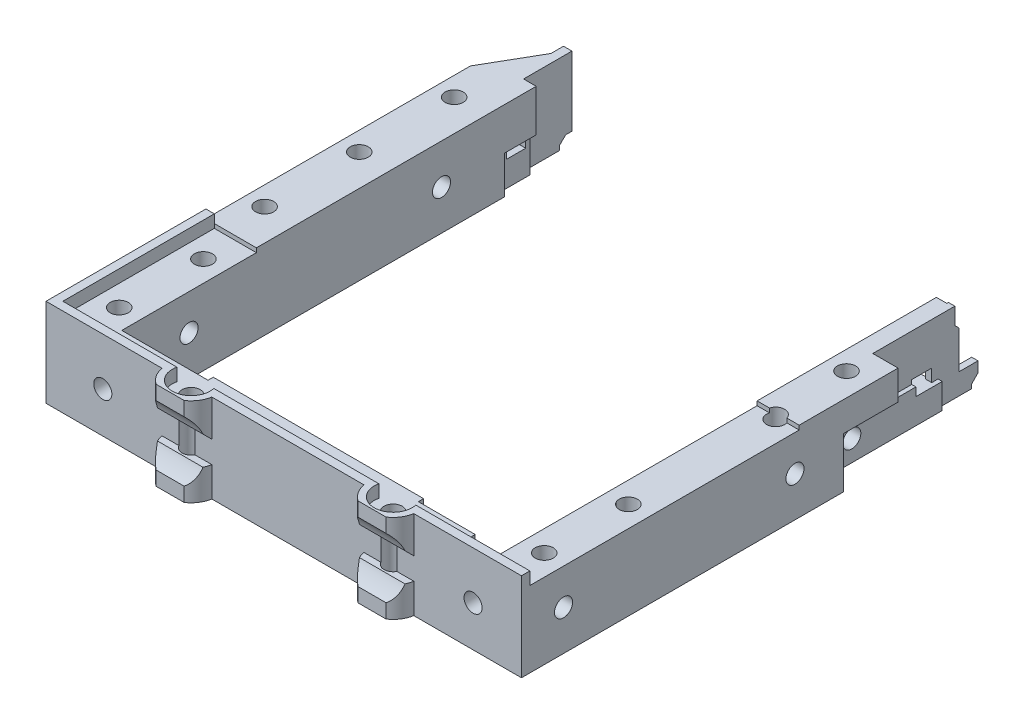
SolidWorks part; units mm, degrees
ref_plane "前视基准面" through (0, 0, 0) normal (0, 0, 1) x (1, 0, 0)
ref_plane "上视基准面" through (0, 0, 0) normal (0, 1, 0) x (1, 0, 0)
ref_plane "右视基准面" through (0, 0, 0) normal (1, 0, 0) x (0, 0, -1)
sketch "草图2" plane through (0, 0, 0) normal (0, 1, 0) x (1, 0, 0)
  line L0 (0, 0) -> (0, -10) construction
  line L1 (-45.5, 0) -> (45.5, 0)
  line L2 (45.5, 0) -> (45.5, 93)
  line L3 (45.5, 93) -> (55.5, 93)
  line L4 (55.5, 93) -> (55.5, -10)
  line L5 (55.5, -10) -> (-55.5, -10)
  line L6 (-45.5, 93) -> (-55.5, 93)
  line L7 (-55.5, 93) -> (-55.5, -10)
  line L8 (-45.5, 0) -> (-45.5, 93)
  dimension "D1" = 10
  dimension "D2" = 10
  dimension "D3" = 45.5
  dimension "D4" = 93
extrude "凸台-拉伸1" add sketch "草图2" along normal blind 18
sketch "草图3" plane through (0, 18, 0) normal (0, 1, 0) x (1, 0, 0)
  line L0 (55.5, 93) -> (45.5, 93) construction
  line L1 (45.5, 93) -> (45.5, 0) construction
  circle A0 centre (50, 76.75) radius 2.15
  dimension "D1" = 16.25
  dimension "D2" = 4.3
  dimension "D3" = 4.5
extrude "切除-拉伸1" cut sketch "草图3" against normal through all
sketch "草图4" plane through (55.5, 0, 0) normal (1, 0, 0) x (0, 0, -1)
  line L0 (-10, 0) -> (93, 0) construction
  line L1 (93, 18) -> (85.5, 18)
  line L2 (93, 18) -> (93, 0)
  line L3 (93, 0) -> (85.5, 0)
  line L4 (85.5, 18) -> (85.5, 0)
  line L5 (93, 18) -> (85.5, 0) construction
  line L6 (93, 0) -> (85.5, 18) construction
  point P4 (89.25, 9)
  dimension "D1" = 7.5
extrude "切除-拉伸2" cut sketch "草图4" against normal blind 6
sketch "草图5" plane through (55.5, 0, 0) normal (1, 0, 0) x (0, 0, -1)
  line L0 (85.5, 18) -> (85.5, 0) construction
  line L1 (85.5, 12) -> (70.5, 12)
  line L2 (85.5, 12) -> (85.5, 0)
  line L3 (85.5, 0) -> (70.5, 0)
  line L4 (70.5, 12) -> (70.5, 0)
  line L5 (85.5, 12) -> (70.5, 0) construction
  line L6 (85.5, 0) -> (70.5, 12) construction
  line L7 (-10, 0) -> (85.5, 0) construction
  line L8 (-10, 18) -> (85.5, 18) construction
  point P4 (78, 6)
  dimension "D1" = 6
  dimension "D2" = 15
extrude "切除-拉伸3" cut sketch "草图5" against normal up to surface (6 mm away) up to face at (49.5, 9, -89.25)
sketch "草图6" plane through (49.5, 0, 0) normal (1, 0, 0) x (0, 0, -1)
  line L1 (93, 0) -> (91, 0)
  line L2 (93, 0) -> (93, 9)
  line L3 (93, 9) -> (91, 9)
  line L4 (91, 0) -> (91, 9)
  line L5 (93, 0) -> (91, 9) construction
  line L6 (93, 9) -> (91, 0) construction
  point P4 (92, 4.5)
  dimension "D1" = 9
  dimension "D2" = 2
extrude "切除-拉伸4" cut sketch "草图6" against normal up to next
sketch "草图7" plane through (0, 18, 0) normal (0, 1, 0) x (1, 0, 0)
  line L0 (-45.5, 0) -> (-45.5, 93) construction
  line L1 (-55.5, 93) -> (-45.5, 93)
  line L2 (-55.5, 93) -> (-55.5, 32)
  line L3 (-55.5, 32) -> (-45.5, 32)
  line L4 (-45.5, 93) -> (-45.5, 32)
  line L5 (-55.5, 93) -> (-45.5, 32) construction
  line L6 (-55.5, 32) -> (-45.5, 93) construction
  point P4 (-50.5, 62.5)
  dimension "D1" = 61
extrude "凸台-拉伸2" add sketch "草图7" along normal blind 1
sketch "草图8" plane through (-55.5, 0, 0) normal (-1, 0, 0) x (0, 0, 1)
  line L1 (-32, 19) -> (-93, 19)
  line L2 (-32, 19) -> (-32, 0)
  line L3 (-32, 0) -> (-93, 0)
  line L4 (-93, 19) -> (-93, 0)
  line L5 (-32, 19) -> (-93, 0) construction
  line L6 (-32, 0) -> (-93, 19) construction
  point P4 (-62.5, 9.5)
extrude "凸台-拉伸3" add sketch "草图8" along normal blind 4
sketch "草图9" plane through (-55.5, 0, 0) normal (-1, 0, 0) x (0, 0, 1)
  line L1 (10, 0) -> (-32, 0)
  line L2 (10, 0) -> (10, 19)
  line L3 (10, 19) -> (-32, 19)
  line L4 (-32, 0) -> (-32, 19)
  line L5 (10, 0) -> (-32, 19) construction
  line L6 (10, 19) -> (-32, 0) construction
  point P4 (-11, 9.5)
extrude "凸台-拉伸4" add sketch "草图9" along normal blind 2
sketch "草图10" plane through (0, 18, 0) normal (0, 1, 0) x (1, 0, 0)
  line L0 (-57.5, -10) -> (-57.5, 32) construction
  line L1 (-55.5, -10) -> (55.5, -10) construction
  circle A0 centre (-50.5, 4.4) radius 2.15
  circle A1 centre (-50.5, 24.4) radius 2.15
  circle A2 centre (-24, -5) radius 2.15
  circle A3 centre (24, -5) radius 2.15
  dimension "D1" = 4.3
  dimension "D2" = 7
  dimension "D3" = 14.4
  dimension "D4" = 20
  dimension "D5" = 5
  dimension "D6" = 33.5
  dimension "D7" = 48
extrude "切除-拉伸5" cut sketch "草图10" against normal blind 6
sketch "草图11" plane through (0, 0, 0) normal (0, 0, -1) x (-1, 0, 0)
  line L0 (-45.5, 18) -> (45.5, 18) construction
  line L1 (-25, 18) -> (25, 18)
  line L2 (-25, 18) -> (-25, 0)
  line L3 (-25, 0) -> (25, 0)
  line L4 (25, 18) -> (25, 0)
  line L5 (-25, 18) -> (25, 0) construction
  line L6 (-25, 0) -> (25, 18) construction
  line L7 (-45.5, 0) -> (45.5, 0) construction
  point P4 (0, 9)
  dimension "D1" = 50
extrude "凸台-拉伸5" add sketch "草图11" along normal blind 1.25
sketch "草图12" plane through (0, 18, 0) normal (0, 1, 0) x (1, 0, 0)
  line L0 (49.5, 93) -> (45.5, 93)
  line L1 (45.5, 93) -> (45.5, 60)
  line L2 (45.5, 93) -> (45.5, 0) construction
  line L3 (45.5, 60) -> (55.5, 60)
  line L4 (55.5, -10) -> (55.5, 85.5) construction
  line L5 (55.5, 60) -> (55.5, 85.5)
  line L6 (55.5, 85.5) -> (49.5, 85.5)
  line L7 (49.5, 85.5) -> (49.5, 93)
  circle A0 centre (50, 76.75) radius 2.15 construction
  circle A1 centre (50, 76.75) radius 2.15
  dimension "D1" = 33
extrude "凸台-拉伸6" add sketch "草图12" along normal blind 1
sketch "草图13" plane through (0, 18, 0) normal (0, 1, 0) x (1, 0, 0)
  line L1 (45.5, 0) -> (38.5, 0)
  line L2 (45.5, 0) -> (45.5, -2)
  line L3 (45.5, -2) -> (38.5, -2)
  line L4 (38.5, 0) -> (38.5, -2)
  line L5 (45.5, 0) -> (38.5, -2) construction
  line L6 (45.5, -2) -> (38.5, 0) construction
  point P4 (42, -1)
  dimension "D1" = 7
  dimension "D2" = 2
extrude "切除-拉伸6" cut sketch "草图13" against normal up to surface (18 mm away) up to face at (4.075, 0, -39.3889)
sketch "草图14" plane through (0, 18, 0) normal (0, 1, 0) x (1, 0, 0)
  line L0 (55.5, -10) -> (55.5, 60) construction
  line L1 (-57.5, -10) -> (-27.3166, -10)
  line L2 (-57.5, -10) -> (-57.5, -6)
  line L3 (-57.5, -6) -> (-29.9161, -6)
  line L4 (55.5, -10) -> (55.5, -6)
  line L5 (-18.0839, -6) -> (18.0839, -6)
  line L6 (-20.6834, -10) -> (20.6834, -10)
  line L7 (29.9161, -6) -> (55.5, -6)
  line L8 (27.3166, -10) -> (55.5, -10)
  arc A0 (-29.9161, -6) -> (-27.3166, -10) centre (-24, -5) ccw
  arc A1 (18.0839, -6) -> (20.6834, -10) centre (24, -5) ccw
  arc A2 (-20.6834, -10) -> (-18.0839, -6) centre (-24, -5) ccw
  arc A3 (27.3166, -10) -> (29.9161, -6) centre (24, -5) ccw
  dimension "D2" = 12
  dimension "D3" = 12
  dimension "D1" = 4
extrude "切除-拉伸7" cut sketch "草图14" against normal through all and the other way through all
sketch "草图16" plane through (0, 18, 0) normal (0, 1, 0) x (1, 0, 0)
  line L0 (55.5, -6) -> (55.5, 60) construction
  line L1 (-55.5, -6) -> (-29.9161, -6)
  line L2 (-55.5, -6) -> (-55.5, -4)
  line L3 (-55.5, -4) -> (-29.9161, -4)
  line L4 (55.5, -6) -> (55.5, -4)
  line L5 (-18.0839, -4) -> (18.0839, -4)
  line L6 (-18.0839, -6) -> (18.0839, -6)
  line L7 (29.9161, -4) -> (55.5, -4)
  line L8 (29.9161, -6) -> (55.5, -6)
  arc A0 (-29.9161, -4) -> (-29.9161, -6) centre (-24, -5) ccw
  arc A1 (18.0839, -4) -> (18.0839, -6) centre (24, -5) ccw
  arc A2 (-18.0839, -6) -> (-18.0839, -4) centre (-24, -5) ccw
  arc A3 (29.9161, -6) -> (29.9161, -4) centre (24, -5) ccw
  dimension "D1" = 2
extrude "凸台-拉伸7" add sketch "草图16" along normal up to surface (1 mm away) up to face at (-54.5, 19, -37.75)
sketch "草图18" plane through (0, 19, 0) normal (0, 1, 0) x (1, 0, 0)
  line L0 (-53, 86.45) -> (-53, 41.45) construction
  line L1 (-59.5, 32) -> (-59.5, 93) construction
  line L2 (-45.5, 93) -> (-59.5, 93) construction
  circle A0 centre (-53, 86.45) radius 2.15
  circle A1 centre (-53, 63.95) radius 2.15
  circle A2 centre (-53, 41.45) radius 2.15
  dimension "D1" = 4.3
  dimension "D2" = 6.5
  dimension "D3" = 6.55
  dimension "D4" = 45
extrude "切除-拉伸8" cut sketch "草图18" against normal blind 6
sketch "草图19" plane through (0, 12, 0) normal (0, 1, 0) x (1, 0, 0)
  circle A0 centre (24, -5) radius 2.15 construction
  circle A1 centre (-24, -5) radius 2.15 construction
  circle A2 centre (24, -5) radius 2.15
  circle A3 centre (-24, -5) radius 2.15
extrude "切除-拉伸9" cut sketch "草图19" against normal through all
sketch "草图20" plane through (0, 13, 0) normal (0, 1, 0) x (1, 0, 0)
  line L0 (0, 0) -> (0, 86.45) construction
  circle A0 centre (-50.5, 4.4) radius 2.15 construction
  circle A1 centre (-50.5, 24.4) radius 2.15 construction
  circle A2 centre (-53, 41.45) radius 2.15 construction
  circle A3 centre (-53, 63.95) radius 2.15 construction
  circle A4 centre (-53, 86.45) radius 2.15 construction
  circle A5 centre (-50.5, 4.4) radius 2.15
  circle A6 centre (-50.5, 24.4) radius 2.15
  circle A7 centre (-53, 41.45) radius 2.15
  circle A8 centre (-53, 63.95) radius 2.15
  circle A9 centre (-53, 86.45) radius 2.15
  circle A10 centre (50.5, 24.4) radius 2.15
  circle A11 centre (50.5, 4.4) radius 2.15
extrude "切除-拉伸10" cut sketch "草图20" against normal through all and the other way through all
sketch "草图21" plane through (0, 0, 0) normal (0, -1, 0) x (1, 0, 0)
  line L1 (-45.5, -93) -> (45.5, -93)
  line L2 (-45.5, -93) -> (-45.5, 2)
  line L3 (-45.5, 2) -> (45.5, 2)
  line L4 (45.5, -93) -> (45.5, 2)
extrude "凸台-拉伸8" [suppressed] add sketch "草图21" against normal blind 2
sketch "草图22" [suppressed] plane through (0, 2, 0) normal (0, 1, 0) x (1, 0, 0)
  line L1 (38.5, 0) -> (45.5, 0)
  line L2 (38.5, 0) -> (38.5, -2)
  line L3 (38.5, -2) -> (45.5, -2)
  line L4 (45.5, 0) -> (45.5, -2)
extrude "凸台-拉伸9" [suppressed] add sketch "草图22" along normal blind 15
sketch "草图23" plane through (0, 0, -32) normal (0, 0, 1) x (1, 0, 0)
  line L4 (-59.5, 0) -> (-57.5, 0)
  line L5 (-57.5, 0) -> (-57.5, 19)
  line L6 (-57.5, 19) -> (-59.5, 19)
  line L7 (-59.5, 19) -> (-59.5, 0)
  line L8 (-59.5, 0) -> (-57.5, 0)
  line L9 (-57.5, 0) -> (-57.5, 19)
  line L10 (-57.5, 19) -> (-59.5, 19)
  line L11 (-59.5, 19) -> (-59.5, 0)
  dimension "D1" = 0
extrude "切除-拉伸11" cut sketch "草图23" against normal through all
sketch "草图24" plane through (0, 19, 0) normal (0, 1, 0) x (1, 0, 0)
  line L0 (-45.5, 93) -> (-49.5, 93)
  line L1 (-45.5, 93) -> (-57.5, 93) construction
  line L2 (-49.5, 93) -> (-45.5, 89)
  line L3 (-45.5, 32) -> (-45.5, 93) construction
  line L4 (-45.5, 89) -> (-45.5, 93)
  dimension "D1" = 4
  dimension "D2" = 4
sketch "草图26" plane through (49.5, 0, 0) normal (1, 0, 0) x (0, 0, -1)
  line L0 (91, 0) -> (91, 6)
  line L2 (91, 9) -> (91, 0) construction
  line L3 (91, 6) -> (98, 6)
  line L4 (98, 6) -> (98, 9)
  line L5 (98, 9) -> (93, 9)
  line L6 (93, 9) -> (93, 19)
  line L7 (93, 19) -> (107, 19)
  line L8 (107, 19) -> (107, 0)
  line L9 (107, 0) -> (91, 0)
  dimension "D1" = 6
  dimension "D2" = 5
  dimension "D3" = 16
extrude "凸台-拉伸10" add sketch "草图26" against normal offset from surface (3 mm away) 1 contours L8 L9 L0 L3 L4 L5 L6 L7 up to face at (45.5, 11.5, -60.5)
sketch "草图27" plane through (46.5, 0, 0) normal (-1, 0, 0) x (0, 0, 1)
  line L0 (-98, 13) -> (-98, 0)
  line L1 (-91, 0) -> (-107, 0) construction
  line L2 (-98, 0) -> (-107, 0)
  line L3 (-107, 0) -> (-107, 19)
  line L4 (-98, 9) -> (-98, 6) construction
  line L5 (-93, 9) -> (-98, 9) construction
  line L6 (-98, 13) -> (-101.4641, 19)
  line L7 (-107, 19) -> (-93, 19) construction
  line L8 (-107, 19) -> (-101.4641, 19)
  dimension "D1" = 4
  dimension "D2" = 150
extrude "切除-拉伸13" cut sketch "草图27" against normal offset from surface (1.5 mm away) 2.5 up to face at (45.5, 11.5, -60.5)
sketch "草图28" plane through (46.5, 0, 0) normal (-1, 0, 0) x (0, 0, 1)
  line L5 (-101.4641, 19) -> (-98, 13)
  line L6 (-98, 13) -> (-98, 9)
  line L7 (-98, 9) -> (-93, 9)
  line L8 (-93, 9) -> (-93, 19)
  line L9 (-93, 19) -> (-101.4641, 19)
  line L10 (-101.4641, 19) -> (-98, 13)
  line L11 (-98, 13) -> (-98, 9)
  line L12 (-98, 9) -> (-93, 9)
  line L13 (-93, 9) -> (-93, 19)
  line L14 (-93, 19) -> (-101.4641, 19)
  dimension "D1" = 0
extrude "凸台-拉伸11" add sketch "草图28" along normal up to surface (1 mm away) up to face at (45.5, 11.5, -60.5)
sketch "草图29" plane through (49.5, 0, 0) normal (1, 0, 0) x (0, 0, -1)
  line L0 (85.5, 12) -> (85.5, 6)
  line L1 (85.5, 6) -> (99, 6)
  line L3 (99, 6) -> (99, 0)
  line L4 (99, 0) -> (78.8411, 0)
  line L5 (70.5, 0) -> (70.5, 12)
  line L6 (70.5, 12) -> (74.6589, 12)
  line L7 (98, 6) -> (98, 9) construction
  line L8 (91, 6) -> (98, 6) construction
  line L9 (78.8411, 12) -> (78.8411, 0)
  line L10 (78.8411, 0) -> (78.8411, 12) construction
  line L11 (74.6589, 0) -> (74.6589, 12)
  line L12 (78.8411, 12) -> (85.5, 12)
  line L13 (74.6589, 0) -> (70.5, 0)
  dimension "D1" = 1
extrude "凸台-拉伸12" add sketch "草图29" along normal offset from surface (1 mm away) 5 up to face at (45.5, 11.6667, -66.1627)
fillet "圆角1" radius 1 1 edges at (50, 6, -85.5)
sketch "草图30" plane through (49.5, 0, 0) normal (1, 0, 0) x (0, 0, -1)
  line L2 (107, 19) -> (107, 0) construction
  line L3 (107, 11) -> (107, 19)
  line L4 (107, 19) -> (101.5, 19)
  line L6 (107, 11) -> (102.5, 11)
  line L7 (101.5, 12) -> (101.5, 19)
  line L8 (85.5, 19) -> (85.5, 12) construction
  arc A0 (102.5, 11) -> (101.5, 12) centre (102.5, 12) cw
  dimension "D2" = 1
  dimension "D1" = 8
  dimension "D3" = 16
extrude "切除-拉伸14" cut sketch "草图30" against normal up to next
sketch "草图31" plane through (49.5, 0, 0) normal (1, 0, 0) x (0, 0, -1)
  line L0 (107, 1) -> (108.5, 2.5)
  line L1 (107, 11) -> (107, 0) construction
  line L2 (108.5, 2.5) -> (108.5, 11)
  line L3 (108.5, 11) -> (107, 11)
  line L6 (99, 0) -> (107, 0) construction
  line L8 (107, 11) -> (107, 1)
  dimension "D1" = 1.5
  dimension "D2" = 1
  dimension "D3" = 45
extrude "凸台-拉伸13" add sketch "草图31" against normal up to surface (1.5 mm away) up to face at (48, 9.9793, -101.2757)
sketch "草图32" plane through (49.5, 0, 0) normal (1, 0, 0) x (0, 0, -1)
  line L0 (99, 6) -> (86.5, 6) construction
  line L1 (91, 9) -> (92.75, 9)
  line L2 (91, 9) -> (91, 6)
  line L3 (91, 6) -> (92.75, 6)
  line L4 (92.75, 9) -> (92.75, 6)
  dimension "D1" = 1.75
extrude "凸台-拉伸14" add sketch "草图32" against normal up to surface (4 mm away) up to face at (45.5, 11.6667, -66.1627)
chamfer "倒角1" distance 1 angle 60 1 edges at (45.5, 6, -91.875) first distance on face at (46, 6, -91.875)
sketch "草图33" plane through (0, 19, 0) normal (0, 1, 0) x (1, 0, 0)
  circle A0 centre (-53, 86.45) radius 2.15
  circle A1 centre (-53, 86.45) radius 2.15 construction
extrude "凸台-拉伸16" add sketch "草图33" against normal up to surface (19 mm away) up to face at (19.4221, 0, -39.5712)
sketch "草图34" plane through (0, 19, 0) normal (0, 1, 0) x (1, 0, 0)
  line L1 (-45.5, 93) -> (-57.5, 93) construction
  line L2 (-53, 86.5) -> (-53, 63.95) construction
  circle A0 centre (-53, 86.5) radius 2.15
  circle A1 centre (-53, 63.95) radius 2.15 construction
  dimension "D2" = 6.5
extrude "切除-拉伸15" cut sketch "草图34" against normal up to next
sketch "草图35" plane through (0, 19, 0) normal (0, 1, 0) x (1, 0, 0)
  circle A0 centre (-53, 86.5) radius 5
  circle A1 centre (-53, 86.5) radius 2.15
  circle A2 centre (-53, 86.5) radius 2.15 construction
  dimension "D1" = 10
sketch "草图36" plane through (-57.5, 0, 0) normal (-1, 0, 0) x (0, 0, 1)
  line L0 (-93, 6) -> (-98.5, 6)
  line L1 (-93, 0) -> (-93, 19) construction
  line L2 (-98.5, 6) -> (-98.5, 9)
  line L3 (-98.5, 9) -> (-93, 9)
  line L4 (-91, 0) -> (-98, 0) construction
  line L5 (-92.75, 9) -> (-98, 9) construction
  line L6 (-93, 6) -> (-93, 0)
  line L7 (-93, 0) -> (-107, 0)
  line L8 (-107, 0) -> (-98, 0) construction
  line L9 (-93, 0) -> (6, 0) construction
  line L10 (-107, 0) -> (-107, 1)
  line L11 (-107, 1) -> (-108.5, 2.5)
  line L12 (-108.5, 2.5) -> (-110, 2.5)
  line L13 (-110, 2.5) -> (-110, 19)
  line L14 (-110, 19) -> (-93, 19)
  line L15 (-93, 19) -> (-93, 9)
  dimension "D1" = 5.5
  dimension "D2" = 6
  dimension "D3" = 14
  dimension "D4" = 1.5
extrude "凸台-拉伸18" add sketch "草图36" against normal up to surface (12 mm away) up to face at (-45.5, 12.3333, -41.6667)
sketch "草图38" plane through (0, 0, -92.75) normal (0, 0, -1) x (-1, 0, 0)
  line L0 (-46.5, 6) -> (-46.5, 8)
  line L1 (-46.5, 8) -> (-45.5, 9)
  line L2 (-45.5, 0) -> (-45.5, 18) construction
  line L3 (-45.5, 9) -> (-45.5, 6)
  line L4 (-45.5, 6) -> (-46.5, 6)
  dimension "D1" = 45
extrude "切除-拉伸16" cut sketch "草图38" against normal up to surface (1.75 mm away) up to face at (46, 3.433, -91)
sketch "草图39" plane through (-45.5, 0, 0) normal (1, 0, 0) x (0, 0, -1)
  line L0 (110, 2.5) -> (110, 19) construction
  line L1 (91, 9) -> (110, 9)
  line L2 (91, 9) -> (91, 0)
  line L3 (91, 0) -> (110, 0)
  line L4 (110, 9) -> (110, 0)
  line L5 (0, 0) -> (107, 0) construction
  line L6 (93, 9) -> (98.5, 9) construction
  line L7 (93, 9) -> (93, 6) construction
  dimension "D1" = 2
extrude "切除-拉伸17" cut sketch "草图39" against normal blind 1.5
chamfer "倒角2" distance 1.5 angle 45 1 edges at (-47, 9, -92)
sketch "草图40" plane through (-47, 0, 0) normal (1, 0, 0) x (0, 0, -1)
  line L0 (32, 19) -> (110, 19) construction
  line L1 (98.5, 19) -> (110, 19)
  line L2 (98.5, 19) -> (98.5, 0)
  line L3 (98.5, 0) -> (110, 0)
  line L4 (110, 19) -> (110, 0)
  line L5 (110, 9) -> (110, 19) construction
  line L7 (91, 0) -> (107, 0) construction
  line L8 (98.5, 6) -> (98.5, 9) construction
extrude "切除-拉伸18" cut sketch "草图40" against normal blind 1.5 and the other way blind 1.5
sketch "草图41" plane through (-57.5, 0, 0) normal (-1, 0, 0) x (0, 0, 1)
  line L0 (-107, 19) -> (-107, 0)
  line L1 (6, 19) -> (-110, 19) construction
  line L2 (-107, 0) -> (6, 0) construction
  line L3 (-93, 6) -> (-93, 7.5) construction
  line L4 (-107, 19) -> (-110, 19)
  line L5 (-110, 19) -> (-110, 2.5)
  line L6 (-110, 2.5) -> (-107, 0)
  dimension "D1" = 14
extrude "切除-拉伸19" cut sketch "草图41" against normal blind 7
chamfer "倒角3" distance 7 angle 60 1 edges at (-57.5, 9.5, -107) first distance on face at (-52.1667, 6.6667, -107)
sketch "草图42" plane through (0, 9, 0) normal (0, -1, 0) x (1, 0, 0)
  line L1 (-51.5, -93) -> (-51.5, -105.2679)
  line L2 (-57.5, -94.8756) -> (-50.5, -107) construction
  line L3 (-51.5, -105.2679) -> (-57.5, -94.8756)
  line L4 (-48.5, -98.5) -> (-48.5, -107) construction
  line L8 (-57.5, -94.8756) -> (-57.5, -93)
  line L9 (-57.5, -93) -> (-51.5, -93)
  line L10 (-45.5, -93) -> (-57.5, -93) construction
  dimension "D1" = 3
extrude "切除-拉伸20" cut sketch "草图42" along normal up to next
sketch "草图43" plane through (49.5, 0, 0) normal (1, 0, 0) x (0, 0, -1)
  line L0 (104, 23.9473) -> (104, -7.2516) construction
  line L1 (98, 6) -> (98, 9) construction
  line L2 (108.5, 2.5) -> (108.5, 11) construction
  line L3 (104, 11) -> (108.5, 11)
  line L4 (104, 11) -> (104, 4)
  line L5 (104, 4) -> (108.5, 4)
  line L6 (108.5, 11) -> (108.5, 4)
  line L7 (102.5, 11) -> (108.5, 11) construction
  line L8 (99, 6) -> (86.5, 6) construction
  dimension "D1" = 6
  dimension "D2" = 2
extrude "切除-拉伸21" cut sketch "草图43" against normal blind 0.7
fillet "圆角2" radius 2 1 edges at (49.15, 4, -104)
sketch "草图44" plane through (48.8, 0, 0) normal (1, 0, 0) x (0, 0, -1)
  line L0 (108.5, 5) -> (104, 5)
  line L1 (108.5, 4) -> (108.5, 11) construction
  line L2 (104, 11) -> (104, 6) construction
  line L3 (108.5, 11) -> (104, 11) construction
  line L4 (108.5, 5) -> (108.5, 11)
  line L5 (104, 11) -> (104, 6)
  line L6 (108.5, 11) -> (104, 11)
  line L7 (106, 4) -> (108.5, 4) construction
  line L8 (104, 6) -> (104, 5)
  dimension "D1" = 1
extrude "切除-拉伸22" cut sketch "草图44" against normal up to next and the other way up to next
sketch "草图45" plane through (48.8, 0, 0) normal (1, 0, 0) x (0, 0, -1)
  line L3 (108.5, 5) -> (104.2679, 5)
  line L4 (106, 4) -> (108.5, 4)
  line L5 (108.5, 4) -> (108.5, 5)
  line L6 (108.5, 5) -> (104.2679, 5)
  line L7 (106, 4) -> (108.5, 4)
  line L8 (108.5, 4) -> (108.5, 5)
  arc A1 (104.2679, 5) -> (106, 4) centre (106, 6) ccw
  arc A2 (104.2679, 5) -> (106, 4) centre (106, 6) ccw
  dimension "D1" = 0
extrude "凸台-拉伸19" add sketch "草图45" along normal up to surface (0.7 mm away) up to face at (49.5, 7.0927, -99.561)
sketch "草图46" plane through (49.5, 0, 0) normal (1, 0, 0) x (0, 0, -1)
  line L0 (99, 6) -> (86.5, 6) construction
  line L1 (98, 9) -> (97.5, 9)
  line L2 (98, 9) -> (98, 6)
  line L3 (98, 6) -> (97.5, 6)
  line L4 (97.5, 9) -> (97.5, 6)
  dimension "D1" = 0.5
extrude "凸台-拉伸20" add sketch "草图46" against normal up to surface (1.5 mm away) up to face at (48, 8.0923, -102.6969)
sketch "草图47" plane through (-51.5, 0, 0) normal (-1, 0, 0) x (0, 0, 1)
  line L1 (-98.5, 9) -> (-97.5, 9)
  line L2 (-98.5, 9) -> (-98.5, 6)
  line L3 (-98.5, 6) -> (-97.5, 6)
  line L4 (-97.5, 9) -> (-97.5, 6)
extrude "凸台-拉伸21" add sketch "草图47" against normal up to surface (4.5 mm away) up to face at (-47, 4.5, -94.1667)
sketch "草图48" plane through (49.5, 0, 0) normal (1, 0, 0) x (0, 0, -1)
  line L0 (85.5, 7) -> (85.5, 12) construction
  line L1 (85.5, 8) -> (83.5, 8)
  line L2 (85.5, 8) -> (85.5, 19)
  line L3 (85.5, 19) -> (83.5, 19)
  line L4 (83.5, 8) -> (83.5, 19)
  line L5 (60, 19) -> (85.5, 19) construction
  line L6 (92.75, 6) -> (86.5, 6) construction
  dimension "D1" = 2
  dimension "D2" = 2
extrude "切除-拉伸23" cut sketch "草图48" along normal up to next
fillet "圆角3" radius 0.5 2 edges at (50, 8, -85.5) (50, 8, -83.5)
sketch "草图49" plane through (48, 0, 0) normal (-1, 0, 0) x (0, 0, 1)
  line L0 (-98, 11) -> (-102.6188, 19)
  line L1 (-98, 9) -> (-98, 13) construction
  line L2 (-102.6188, 19) -> (-101.4641, 19)
  line L3 (-101.4641, 19) -> (-98, 13)
  line L4 (-98, 13) -> (-98, 11)
  dimension "D1" = 1
extrude "凸台-拉伸22" add sketch "草图49" along normal up to surface (2.5 mm away) up to face at (45.5, 11.4, -68.8214)
sketch "草图50" plane through (49.5, 0, 0) normal (1, 0, 0) x (0, 0, -1)
  line L1 (104, 11) -> (101.5, 11)
  line L2 (104, 11) -> (104, 19)
  line L3 (104, 19) -> (101.5, 19)
  line L4 (101.5, 11) -> (101.5, 19)
extrude "凸台-拉伸23" add sketch "草图50" against normal up to surface (1.5 mm away) up to face at (48, 7.0237, -102.0862)
sketch "草图51" plane through (48, 0, 0) normal (-1, 0, 0) x (0, 0, 1)
  line L1 (-104, 19) -> (-103, 19)
  line L2 (-104, 19) -> (-104, 14)
  line L3 (-104, 14) -> (-103, 14)
  line L4 (-103, 19) -> (-103, 14)
  dimension "D1" = 1
  dimension "D2" = 5
extrude "切除-拉伸24" cut sketch "草图51" against normal up to next
chamfer "倒角4" distance 1 angle 45 1 edges at (48.75, 14, -103)
sketch "草图52" plane through (0, 0, 0) normal (0, -1, 0) x (1, 0, 0)
  line L0 (50.5, -73.792) -> (50.5, -79.708)
  line L1 (50.5, -70.5) -> (50.5, -74.6589) construction
  line L2 (50.5, -83.5) -> (50.5, -78.8411) construction
  arc A0 (50.5, -73.792) -> (50.5, -79.708) centre (50, -76.75) ccw
  dimension "D1" = 6
extrude "凸台-拉伸25" add sketch "草图52" against normal up to surface (12 mm away) up to face at (52.4417, 12, -76.9167)
sketch "草图53" plane through (50.5, 0, 0) normal (1, 0, 0) x (0, 0, -1)
  line L0 (77.5, 12) -> (77.5, 0) construction
  line L1 (83.5, 12) -> (70.5, 12) construction
  line L2 (70.5, 0) -> (99, 0) construction
  line L3 (70.5, 12) -> (70.5, 0) construction
  circle A0 centre (77.5, 5) radius 2.15
  dimension "D1" = 4.3
  dimension "D3" = 5
  dimension "D2" = 7
extrude "切除-拉伸25" cut sketch "草图53" against normal up to next
sketch "草图54" plane through (0, 0, 0) normal (0, -1, 0) x (1, 0, 0)
  line L0 (50.5, -24.4) -> (50.5, -59.4) construction
  circle A0 centre (50.5, -59.4) radius 2.15
  dimension "D1" = 4.3
  dimension "D2" = 35
extrude "切除-拉伸26" cut sketch "草图54" against normal up to next
sketch "草图55" plane through (-57.5, 0, 0) normal (-1, 0, 0) x (0, 0, 1)
  line L0 (6, 9.5) -> (-76, 9.5) construction
  line L1 (6, 0) -> (6, 19) construction
  line L2 (-93, 0) -> (-93, 9) construction
  circle A0 centre (-76, 9.5) radius 2.15
  circle A1 centre (-16, 9.5) radius 2.15
  dimension "D2" = 60
  dimension "D3" = 4.3
  dimension "D1" = 17
extrude "切除-拉伸27" cut sketch "草图55" against normal up to surface (12 mm away) up to face at (-45.5, 11.2222, -59.5556)
sketch "草图56" plane through (55.5, 0, 0) normal (1, 0, 0) x (0, 0, -1)
  line L0 (-6, 9.5) -> (59, 9.5) construction
  line L1 (-6, 0) -> (-6, 19) construction
  circle A0 centre (4, 9.5) radius 2.15
  circle A1 centre (59, 9.5) radius 2.15
  dimension "D2" = 4.3
  dimension "D3" = 55
  dimension "D1" = 65
extrude "切除-拉伸28" cut sketch "草图56" against normal up to surface (10 mm away) up to face at (45.5, 5, -79.65)
sketch "草图57" plane through (55.5, 0, 0) normal (1, 0, 0) x (0, 0, -1)
  line L0 (-6, 10.5) -> (-17, 10.5) construction
  line L2 (-6, 0) -> (-6, 19) construction
  line L3 (-10, 0) -> (-6, 0) construction
  circle A0 centre (-17, 10.5) radius 10
  dimension "D1" = 20
  dimension "D2" = 11
  dimension "D3" = 10.5
extrude "切除-拉伸29" cut sketch "草图57" against normal up to surface (113 mm away) up to face at (-57.5, 9.5, -73.85)
sketch "草图58" plane through (55.5, 0, 0) normal (1, 0, 0) x (0, 0, -1)
  line L0 (-6, 0) -> (-6, 19) construction
  line L1 (-7.6, 13.9117) -> (-6, 13.9117)
  line L2 (-7.6, 13.9117) -> (-7.6, 7.0883)
  line L3 (-7.6, 7.0883) -> (-6, 7.0883)
  line L4 (-6, 13.9117) -> (-6, 7.0883)
  arc A0 (-10, 3.3586) -> (-10, 17.6414) centre (-17, 10.5) ccw construction
  dimension "D1" = 1.6
extrude "切除-拉伸30" cut sketch "草图58" against normal up to surface (113 mm away) up to face at (-57.5, 9.5, -73.85)
chamfer "倒角5" distance 1.6 angle 45 2 edges at (-27.9097, 13.9117, 6) (27.9097, 13.9117, 6)
sketch "草图59" plane through (0, 19, 0) normal (0, 1, 0) x (1, 0, 0)
  line L0 (-55.5, 32) -> (-57.5, 32)
  line L1 (55.5, -6) -> (55.5, -4) construction
  line L2 (55.5, -4) -> (29.9161, -4) construction
  line L3 (29.9161, -6) -> (55.5, -6) construction
  line L4 (-18.0839, -6) -> (18.0839, -6) construction
  line L5 (18.0839, -4) -> (-18.0839, -4) construction
  line L6 (55.5, -6) -> (55.5, -4)
  line L7 (55.5, -4) -> (29.9161, -4)
  line L8 (29.9161, -6) -> (55.5, -6)
  line L9 (-18.0839, -6) -> (18.0839, -6)
  line L10 (18.0839, -4) -> (-18.0839, -4)
  line L11 (-50.5, 110) -> (-50.5, 107)
  line L12 (-50.5, 107) -> (-57.5, 94.8756)
  line L13 (-57.5, 94.8756) -> (-57.5, -6)
  line L14 (-57.5, -6) -> (-29.9161, -6)
  line L15 (-29.9161, -4) -> (-55.5, -4)
  line L16 (-55.5, -4) -> (-55.5, 32)
  line L17 (-55.5, 32) -> (-45.5, 32)
  line L18 (-45.5, 32) -> (-45.5, 98.5)
  line L19 (-45.5, 98.5) -> (-48.5, 98.5)
  line L20 (-48.5, 98.5) -> (-48.5, 110)
  line L21 (-48.5, 110) -> (-50.5, 110)
  line L24 (-57.5, 32) -> (-57.5, -6)
  line L25 (-57.5, -6) -> (-29.9161, -6)
  line L26 (-29.9161, -4) -> (-55.5, -4)
  line L27 (-55.5, -4) -> (-55.5, 32)
  arc A0 (29.9161, -6) -> (29.9161, -4) centre (24, -5) ccw construction
  arc A1 (-29.9161, -4) -> (-29.9161, -6) centre (-24, -5) ccw
  arc A2 (-29.9161, -4) -> (-29.9161, -6) centre (-24, -5) ccw
  arc A3 (18.0839, -4) -> (18.0839, -6) centre (24, -5) ccw construction
  arc A4 (-18.0839, -6) -> (-18.0839, -4) centre (-24, -5) ccw construction
  arc A5 (29.9161, -6) -> (29.9161, -4) centre (24, -5) ccw
  arc A6 (18.0839, -4) -> (18.0839, -6) centre (24, -5) ccw
  arc A7 (-18.0839, -6) -> (-18.0839, -4) centre (-24, -5) ccw
  dimension "D1" = 0
extrude "凸台-拉伸26" add sketch "草图59" along normal blind 2
sketch "草图60" plane through (0, 18, 0) normal (0, 1, 0) x (1, 0, 0)
  line L0 (-29.9161, -4) -> (-28.3875, -4)
  line L1 (-27.3166, -10) -> (-20.6834, -10)
  line L2 (-19.6125, -4) -> (-18.0839, -4)
  line L3 (18.0839, -4) -> (19.6125, -4)
  line L4 (20.6834, -10) -> (27.3166, -10)
  line L5 (28.3875, -4) -> (29.9161, -4)
  arc A0 (-29.9161, -4) -> (-27.3166, -10) centre (-24, -5) ccw
  arc A1 (-28.3875, -4) -> (-19.6125, -4) centre (-24, -5) ccw
  arc A2 (-20.6834, -10) -> (-18.0839, -4) centre (-24, -5) ccw
  arc A3 (18.0839, -4) -> (20.6834, -10) centre (24, -5) ccw
  arc A4 (19.6125, -4) -> (28.3875, -4) centre (24, -5) ccw
  arc A5 (27.3166, -10) -> (29.9161, -4) centre (24, -5) ccw
  dimension "D1" = 1.5
  dimension "D2" = 1.5
extrude "凸台-拉伸27" add sketch "草图60" along normal up to surface (3 mm away) up to face at (-47.6527, 21, -7.3333)
sketch "草图61" plane through (0, 0, 6) normal (0, 0, 1) x (1, 0, 0)
  line L0 (-18.0839, 12.3117) -> (-18.0839, 7.0883) construction
  line L1 (-18.0839, 9.7) -> (-44, 9.7) construction
  line L2 (-18.0839, 9.7) -> (44, 9.7) construction
  line L3 (0, 21) -> (0, 0) construction
  line L4 (-18.0839, 21) -> (18.0839, 21) construction
  circle A0 centre (-44, 9.7) radius 2.15
  circle A1 centre (44, 9.7) radius 2.15
  dimension "D2" = 4.3
  dimension "D1" = 88
extrude "切除-拉伸31" cut sketch "草图61" against normal up to surface (6 mm away) up to face at (-35.25, 9, 0)
sketch "草图62" plane through (49.5, 0, 0) normal (1, 0, 0) x (0, 0, -1)
  line L0 (99, 6) -> (86.5, 6) construction
  line L1 (85, 8) -> (92.75, 8)
  line L2 (85, 8) -> (85, 6)
  line L3 (85, 6) -> (92.75, 6)
  line L4 (92.75, 8) -> (92.75, 6)
extrude "凸台-拉伸28" add sketch "草图62" along normal up to surface (1 mm away) up to face at (50.5, 5, -79.65)
equation "\"1、\"=4"
